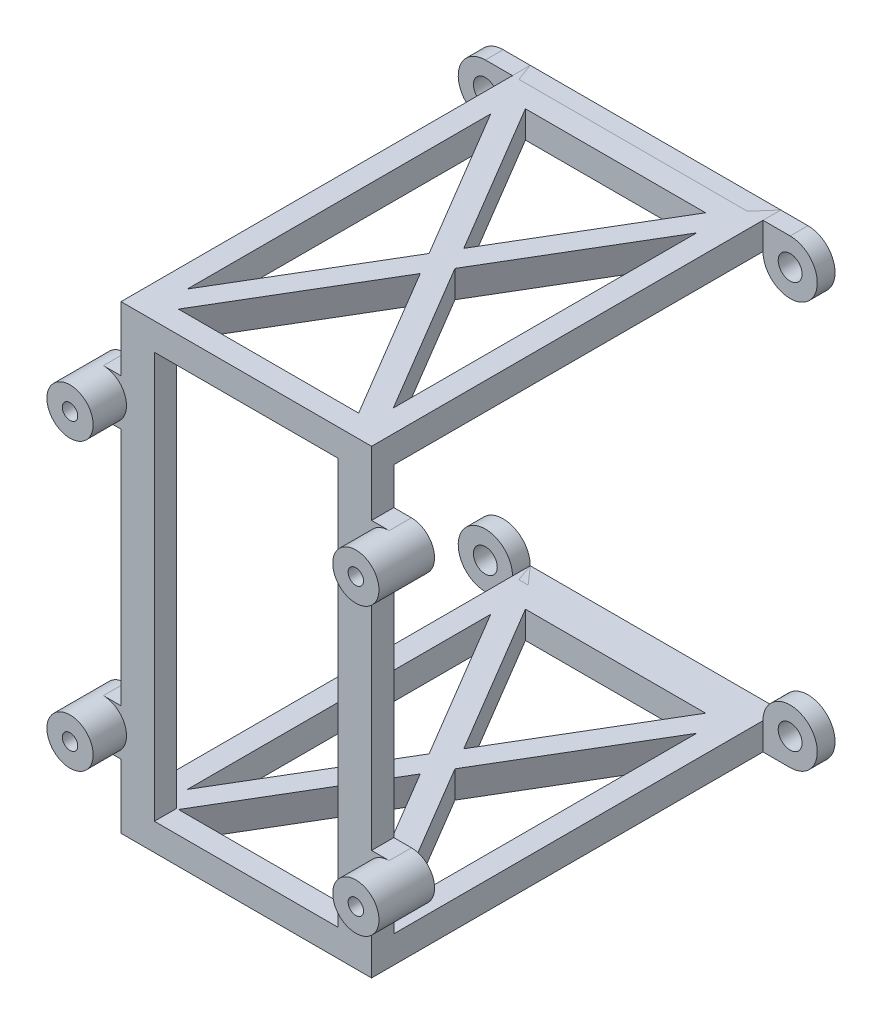
SolidWorks part; units mm, degrees
material "ABS PC"
ref_plane "Front Plane" through (0, 0, 0) normal (0, 0, 1) x (1, 0, 0)
ref_plane "Top Plane" through (0, 0, 0) normal (0, 1, 0) x (1, 0, 0)
ref_plane "Right Plane" through (0, 0, 0) normal (1, 0, 0) x (0, 0, -1)
sketch "Sketch1" plane through (0, 0, 0) normal (0, 0, 1) x (1, 0, 0)
  line L0 (-21.7551, 32.8676) -> (21.7551, 32.8676)
  line L1 (-21.7551, -28.9941) -> (21.7551, -28.9941) construction
  line L2 (-21.7551, -28.9941) -> (-21.7551, 28.9941) construction
  line L3 (-21.7551, 28.9941) -> (21.7551, 28.9941) construction
  line L4 (21.7551, -28.9941) -> (21.7551, 28.9941) construction
  line L5 (-21.7551, -28.9941) -> (21.7551, 28.9941) construction
  line L6 (-21.7551, 28.9941) -> (21.7551, -28.9941) construction
  line L7 (-21.7551, -32.8676) -> (21.7551, -32.8676)
  line L8 (-17.8816, 28.9941) -> (17.8816, 28.9941)
  line L9 (-17.8816, -28.9941) -> (17.8816, -28.9941)
  line L15 (-19.4303, -25.8958) -> (19.4303, 25.8958) construction
  line L16 (-19.4303, 25.8958) -> (19.4303, -25.8958) construction
  circle A0 centre (-21.7551, 28.9941) radius 3.8735
  circle A1 centre (21.7551, 28.9941) radius 3.8735
  circle A2 centre (21.7551, 28.9941) radius 1.7018
  circle A3 centre (-21.7551, 28.9941) radius 1.7018
  circle A4 centre (-21.7551, -28.9941) radius 3.8735
  circle A5 centre (-21.7551, -28.9941) radius 1.7018
  circle A6 centre (21.7551, -28.9941) radius 1.7018
  circle A7 centre (21.7551, -28.9941) radius 3.8735
  point P0 (0, 0)
  point P22 (0, 0)
  dimension "D3" = 7.747
  dimension "D4" = 3.4036
  dimension "D1" = 43.5102
  dimension "D2" = 57.9882
extrude "Boss-Extrude2" add sketch "Sketch1" along normal blind 2.54 contours A4 A0 | A0 A3 | A1 L0 A0 | A1 A2 | A7 A1 | A7 A6 | A7 A4 L7 | A4 A5 region at (0, 30.9784, 0) region at (-19.0936, 31.6556, 0) region at (24.4166, 31.6556, 0) region at (0, -30.9784, 0) region at (-24.4166, -26.3326, 0) region at (19.0936, -31.6556, 0)
sketch "Sketch2" plane through (0, 0, 2.54) normal (0, 0, 1) x (1, 0, 0)
  line L4 (-17.8816, 28.9941) -> (17.8816, 28.9941)
  line L9 (-17.8816, -28.9941) -> (17.8816, -28.9941)
  line L10 (17.8816, -28.9941) -> (17.8816, -32.8676)
  line L11 (17.8816, 28.9941) -> (17.8816, 32.8676)
  line L12 (-21.7551, 32.8676) -> (21.7551, 32.8676) construction
  line L13 (17.8816, 32.8676) -> (-17.8816, 32.8676)
  line L14 (-17.8816, 32.8676) -> (-17.8816, 28.9941)
  line L15 (-21.7551, -32.8676) -> (21.7551, -32.8676) construction
  line L16 (17.8816, -32.8676) -> (-17.8816, -32.8676)
  line L17 (-17.8816, -32.8676) -> (-17.8816, -28.9941)
  point P4 (0, 0)
extrude "Boss-Extrude3" add sketch "Sketch2" along normal blind 58.42 from surface separate body starting at face at (0, -28.593, 0)
sketch "Sketch6" plane through (0, 32.8676, 0) normal (0, 1, 0) x (1, 0, 0)
  line L0 (-17.8816, -2.54) -> (17.8816, -2.54)
  line L1 (-21.7551, -2.54) -> (21.7551, -2.54) construction
  line L2 (-12.8603, -55.245) -> (14.7066, -8.8241)
  line L3 (-14.7066, -55.245) -> (14.7066, -55.245)
  line L4 (17.8816, 0) -> (-17.8816, 0)
  line L5 (-17.8816, 0) -> (-17.8816, -58.42)
  line L6 (-17.8816, -58.42) -> (17.8816, -58.42)
  line L7 (17.8816, -58.42) -> (17.8816, 0)
  line L9 (-17.8816, -2.54) -> (-17.8816, -58.42)
  line L10 (-17.8816, -58.42) -> (17.8816, -58.42)
  line L11 (17.8816, -58.42) -> (17.8816, -2.54)
  line L12 (-14.7066, -55.245) -> (-14.7066, -5.715)
  line L13 (-14.7066, -5.715) -> (14.7066, -5.715)
  line L14 (14.7066, -55.245) -> (14.7066, -5.715)
  line L15 (-14.7066, -55.245) -> (14.7066, -5.715) construction
  line L16 (-14.7066, -5.715) -> (14.7066, -55.245) construction
  line L17 (12.8603, -5.715) -> (-14.7066, -52.1359)
  line L18 (12.8603, -55.245) -> (-14.7066, -8.8241)
  line L19 (-12.8603, -5.715) -> (14.7066, -52.1359)
  point P8 (0, -30.48)
  dimension "D2" = 3.175
  dimension "D3" = 3.175
  dimension "D4" = 3.175
  dimension "D5" = 3.175
  dimension "D6" = 1.5875
  dimension "D7" = 1.5875
  dimension "D8" = 1.5875
  dimension "D9" = 1.5875
  dimension "D1" = 0
extrude "Cut-Extrude3" cut sketch "Sketch6" against normal through all contours L17 L18 L12 | L13 L19 L17 | L2 L19 L14 | L3 L18 L2 region at (0, 32.8676, 48.0264) region at (10.4198, 32.8676, 30.48) region at (-10.4198, 32.8676, 30.48) region at (0, 32.8676, 12.9336)
sketch "Sketch7" plane through (0, 0, 0) normal (0, 0, 1) x (1, 0, 0)
  line L0 (-13.1191, -17.1002) -> (-13.1191, 17.1002)
  line L1 (-20.4, -20.4) -> (20.4, -20.4) construction
  line L2 (-20.4, -20.4) -> (-20.4, 20.4) construction
  line L3 (-20.4, 20.4) -> (20.4, 20.4) construction
  line L4 (20.4, -20.4) -> (20.4, 20.4) construction
  line L5 (-20.4, -20.4) -> (20.4, 20.4) construction
  line L6 (-20.4, 20.4) -> (20.4, -20.4) construction
  line L7 (-17.8816, 32.8676) -> (-17.8816, 23.6999)
  line L8 (-20.4, 23.6999) -> (-17.8816, 23.6999)
  line L9 (-13.1191, 32.8676) -> (-13.1191, 17.1002)
  line L10 (-20.4, 17.1002) -> (-17.8816, 17.1002)
  line L11 (13.1191, 32.8676) -> (13.1191, 17.1002)
  line L12 (17.8816, 17.1002) -> (20.4, 17.1002)
  line L13 (20.4, 23.6999) -> (17.8816, 23.6999)
  line L14 (17.8816, 32.8676) -> (17.8816, 23.6999)
  line L15 (-13.1191, -32.8676) -> (-13.1191, -17.1002)
  line L16 (-20.4, -17.1002) -> (-17.8816, -17.1002)
  line L17 (-20.4, -23.6999) -> (-17.8816, -23.6999)
  line L18 (-17.8816, -23.6999) -> (-17.8816, -32.8676)
  line L19 (-17.8816, -32.8676) -> (-13.1191, -32.8676)
  line L20 (-17.8816, 32.8676) -> (-13.1191, 32.8676)
  line L21 (13.1191, 32.8676) -> (17.8816, 32.8676)
  line L22 (20.4, -17.1002) -> (17.8816, -17.1002)
  line L23 (13.1191, -17.1002) -> (13.1191, -32.8676)
  line L24 (-17.8816, -32.8676) -> (17.8816, -32.8676) construction
  line L25 (13.1191, -32.8676) -> (17.8816, -32.8676)
  line L26 (17.8816, -32.8676) -> (17.8816, -23.6999)
  line L27 (17.8816, -23.6999) -> (20.4, -23.6999)
  line L28 (-17.8816, 17.1002) -> (-17.8816, -17.1002)
  line L29 (13.1191, 17.1002) -> (13.1191, -17.1002)
  line L30 (17.8816, 17.1002) -> (17.8816, -17.1002)
  circle A0 centre (20.4, 20.4) radius 3.2998
  circle A1 centre (-20.4, 20.4) radius 3.2998
  circle A2 centre (-20.4, -20.4) radius 3.2998
  circle A3 centre (20.4, -20.4) radius 3.2998
  circle A4 centre (-20.4, 20.4) radius 1.0999
  circle A5 centre (20.4, 20.4) radius 1.0999
  circle A6 centre (-20.4, -20.4) radius 1.0999
  circle A7 centre (20.4, -20.4) radius 1.0999
  point P0 (0, 0)
  dimension "D3" = 6.5997
  dimension "D8" = 2.1999
  dimension "D1" = 40.8
  dimension "D2" = 40.8
  dimension "D4" = 4.7625
  dimension "D5" = 4.7625
  dimension "D6" = 4.7625
  dimension "D7" = 4.7625
extrude "Boss-Extrude4" add sketch "Sketch7" against normal blind 3.175 from surface contours A1 L10 L9 L20 L7 L8 | A1 | A0 | A0 L13 L14 L21 L11 L12 | A3 L22 L23 L25 L26 L27 | A3 | A2 | A2 L17 L18 L19 L15 L16 region at (-15.5046, 0, 0) region at (-23.6065, -20.4, 0) region at (-18.1327, 22.6674, 0) region at (15.5046, 0, 0) region at (22.6674, 22.6674, 0) region at (17.1935, -20.4, 0) starting at face at (0, 30.9308, 58.42)
sketch "Sketch8" plane through (0, 0, 58.42) normal (0, 0, 1) x (1, 0, 0)
  circle A0 centre (-20.4, 20.4) radius 3.2998
  circle A1 centre (-20.4, 20.4) radius 1.0999
  circle A2 centre (20.4, 20.4) radius 1.0999
  circle A3 centre (20.4, 20.4) radius 3.2998
  circle A4 centre (20.4, -20.4) radius 1.0999
  circle A5 centre (20.4, -20.4) radius 3.2998
  circle A6 centre (-20.4, -20.4) radius 1.0999
  circle A7 centre (-20.4, -20.4) radius 3.2998
extrude "Boss-Extrude5" add sketch "Sketch8" along normal blind 4.7625
